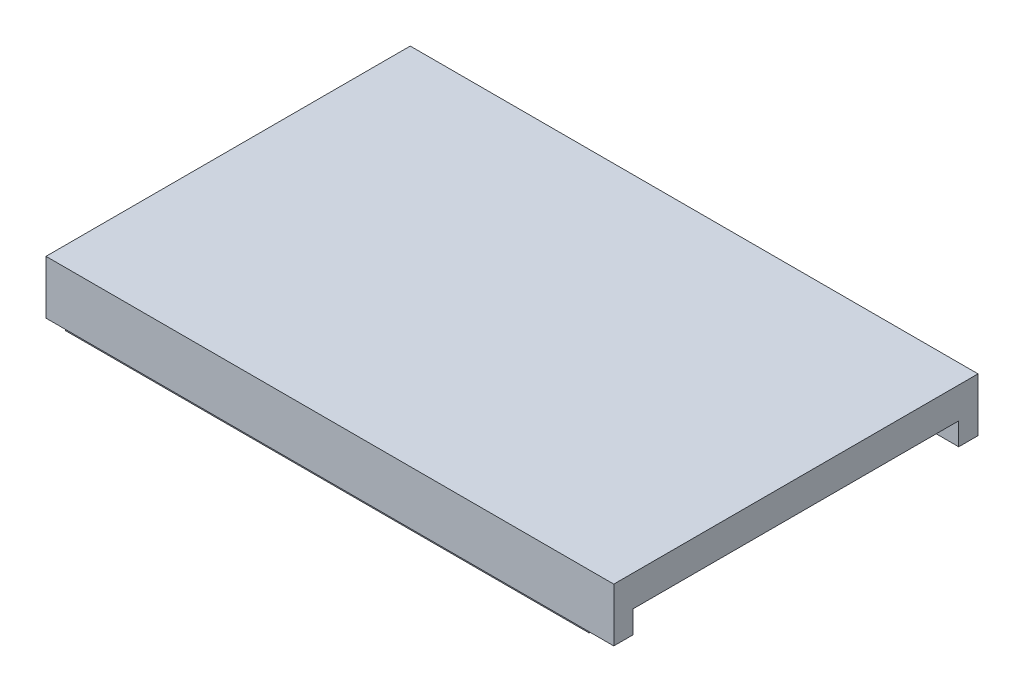
SolidWorks part; units mm, degrees
ref_plane "Front Plane" through (0, 0, 0) normal (0, 0, 1) x (1, 0, 0)
ref_plane "Top Plane" through (0, 0, 0) normal (0, 1, 0) x (1, 0, 0)
ref_plane "Right Plane" through (0, 0, 0) normal (1, 0, 0) x (0, 0, -1)
sketch "Sketch1" plane through (0, 0, 0) normal (0, 1, 0) x (1, 0, 0)
  line L1 (0, 0) -> (53, 0)
  line L2 (0, 0) -> (0, 34)
  line L3 (0, 34) -> (53, 34)
  line L4 (53, 0) -> (53, 34)
  dimension "D1" = 53
  dimension "D2" = 34
extrude "Boss-Extrude1" add sketch "Sketch1" along normal blind 5
sketch "Sketch2" plane through (0, 0, 0) normal (0, -1, 0) x (1, 0, 0)
  line L0 (0, -34) -> (0, 0) construction
  line L1 (1.2, -1.2) -> (49.8, -1.2)
  line L2 (1.2, -1.2) -> (1.2, -32.8)
  line L3 (1.2, -32.8) -> (49.8, -32.8)
  line L4 (49.8, -1.2) -> (49.8, -32.8)
  line L5 (0, 0) -> (53, 0) construction
  line L6 (53, -34) -> (0, -34) construction
  line L7 (53, 0) -> (53, -34) construction
  dimension "D1" = 1.2
  dimension "D2" = 1.2
  dimension "D3" = 1.2
  dimension "D4" = 3.2
extrude "Cut-Extrude1" cut sketch "Sketch2" against normal blind 3.5
sketch "Sketch3" plane through (0, 0, 0) normal (0, -1, 0) x (1, 0, 0)
  line L0 (49.8, -1.2) -> (1.2, -1.2)
  line L1 (1.2, -1.2) -> (1.2, -12)
  line L2 (1.2, -1.2) -> (1.2, -32.8) construction
  line L3 (1.2, -22) -> (1.2, -32.8)
  line L4 (1.2, -32.8) -> (49.8, -32.8)
  line L5 (49.8, -0.9) -> (0.9, -0.9)
  line L6 (0.9, -0.9) -> (0.9, -12)
  line L7 (0.9, -22) -> (0.9, -33.1)
  line L8 (0.9, -33.1) -> (49.8, -33.1)
  line L9 (49.8, -0.9) -> (49.8, -1.2)
  line L10 (0.9, -12) -> (1.2, -12)
  line L11 (0.9, -22) -> (1.2, -22)
  line L12 (49.8, -32.8) -> (49.8, -33.1)
  dimension "D1" = 10.8
  dimension "D2" = 10.8
  dimension "D3" = 0.3
  dimension "D4" = 0.3
extrude "Boss-Extrude2" add sketch "Sketch3" along normal blind 1
sketch "Sketch4" plane through (0, 0, 0) normal (0, -1, 0) x (1, 0, 0)
  line L0 (0, -34) -> (0, 0) construction
  line L1 (1.2, -12) -> (0, -12)
  line L2 (1.2, -12) -> (1.2, -22)
  line L3 (1.2, -22) -> (0, -22)
  line L4 (0, -12) -> (0, -22)
  dimension "D1" = 10
extrude "Cut-Extrude2" cut sketch "Sketch4" against normal blind 0.5
sketch "Sketch5" plane through (0, 0, 0) normal (0, -1, 0) x (1, 0, 0)
  line L0 (49.8, -32.8) -> (49.8, -1.2) construction
  line L1 (49.8, -1.8) -> (53, -1.8)
  line L2 (49.8, -1.8) -> (49.8, -32.2)
  line L3 (49.8, -32.2) -> (53, -32.2)
  line L4 (53, -1.8) -> (53, -32.2)
  line L5 (53, 0) -> (53, -34) construction
  line L6 (0, 0) -> (53, 0) construction
  dimension "D1" = 1.8
  dimension "D2" = 30.4
extrude "Cut-Extrude3" cut sketch "Sketch5" against normal blind 2.1
sketch "Sketch6" plane through (0, 3.5, 0) normal (0, -1, 0) x (1, 0, 0)
  line L1 (1.2, -1.2) -> (6.6, -1.2)
  line L2 (1.2, -1.2) -> (1.2, -6.6)
  line L3 (1.2, -6.6) -> (6.6, -6.6)
  line L4 (6.6, -1.2) -> (6.6, -6.6)
  line L5 (1.2, -32.8) -> (6.6, -32.8)
  line L6 (1.2, -32.8) -> (1.2, -28.5)
  line L7 (1.2, -28.5) -> (6.6, -28.5)
  line L8 (6.6, -32.8) -> (6.6, -28.5)
  dimension "D1" = 5.4
  dimension "D2" = 5.4
  dimension "D3" = 5.4
  dimension "D4" = 4.3
extrude "Boss-Extrude3" add sketch "Sketch6" along normal blind 3
sketch "Sketch7" plane through (0, 0.5, 0) normal (0, -1, 0) x (1, 0, 0)
  line L0 (5, -5) -> (5, -30.5) construction
  line L1 (0, -12) -> (0, 0) construction
  line L2 (0, 0) -> (53, 0) construction
  circle A0 centre (5, -5) radius 1.6
  circle A1 centre (5, -30.5) radius 1.6
  dimension "D4" = 3.2
  dimension "D5" = 3.2
  dimension "D1" = 5
  dimension "D2" = 5
  dimension "D3" = 25.5
extrude "Boss-Extrude4" add sketch "Sketch7" along normal blind 1.2
sketch "Sketch8" plane through (0, -0.7, 0) normal (0, -1, 0) x (1, 0, 0)
  line L0 (5, -5) -> (5, -30.5) construction
  circle A0 centre (5, -5) radius 1
  circle A1 centre (5, -30.5) radius 1
  dimension "D1" = 2
  dimension "D2" = 2
extrude "Cut-Extrude4" cut sketch "Sketch8" against normal blind 5.2
ref_plane "Plane1" through (0, -1.7, 0) normal (0, -1, 0) x (-1, 0, 0)
sketch "Sketch11" plane through (0, -1.7, 0) normal (0, -1, 0) x (-1, 0, 0)
  circle A0 centre (-5, 30.5) radius 0.87
  dimension "D1" = 1.74
curve "Helix/Spiral1" pitch 0.4 height 6 radius 0.87 centre (5, -1.7, -30.5) axis (0, 1, 0) start towards (0, 0, -1)
ref_plane "Plane2" through (5, 0, 0) normal (-1, 0, 0) x (0, 0, 1)
sketch "Sketch13" plane through (5, 0, 0) normal (-1, 0, 0) x (0, 0, 1)
  line L0 (-34, 5) -> (-30.5, 5) construction
  line L1 (-34, 5) -> (0, 5) construction
  line L3 (-30.5, 5) -> (-30.5, -1.7) construction
  line L5 (-30.5, -1.7) -> (-31.2835, -1.7) construction
  line L6 (-30.5, -1.7) -> (-30.5, -3.2) construction
  line L7 (-30.5, -3.2) -> (-31.5, -3.2) construction
  line L8 (-31.5, -3.2) -> (-31.5, -1.2) construction
  line L9 (-31.2835, -1.7) -> (-32.0835, -1.7) construction
  line L10 (-31.2835, -1.75) -> (-31.2835, -1.65) construction
  line L11 (-31.2835, -1.65) -> (-31.7165, -1.4) construction
  line L16 (-31.2835, -1.75) -> (-31.7165, -2) construction
  line L17 (-31.2835, -1.65) -> (-31.5, -1.525)
  line L21 (-31.5, -1.525) -> (-31.5, -1.875)
  line L22 (-31.5, -1.875) -> (-31.2835, -1.75)
  line L23 (-31.2835, -1.75) -> (-31.2835, -1.65)
  dimension "D1" = 3.5
  dimension "D3" = 6.7
  dimension "D5" = 0.7835
  dimension "D6" = 1.5
  dimension "D7" = 1
  dimension "D8" = 2
  dimension "D9" = 0.8
  dimension "D10" = 90
  dimension "D11" = 0.05
  dimension "D12" = 0.1
  dimension "D13" = 0.5
  dimension "D14" = 0.5
  dimension "D15" = 30
  dimension "D16" = 60
  dimension "D17" = 0.35
sweep "Sweep2" add profiles "Sketch13" path "Helix/Spiral1"
pattern_linear "LPattern1" count 2 spacing 25.5 along (0, 0, 1) of "Sweep2"
sketch "Sketch14" plane through (5, 0, 0) normal (-1, 0, 0) x (0, 0, 1)
  line L5 (-34, 5) -> (-34, 0) construction
  line L10 (-32.5, -0.7) -> (-28.5, -0.7)
  line L11 (-32.5, -0.7) -> (-32.5, -3.7)
  line L12 (-32.5, -3.7) -> (-28.5, -3.7)
  line L13 (-28.5, -0.7) -> (-28.5, -3.7)
  line L14 (-32.5, -0.7) -> (-28.5, -3.7) construction
  line L15 (-32.5, -3.7) -> (-28.5, -0.7) construction
  line L16 (-34, 5) -> (0, 5) construction
  line L18 (-7, -0.7) -> (-3, -0.7)
  line L19 (-7, -0.7) -> (-7, -3.7)
  line L20 (-7, -3.7) -> (-3, -3.7)
  line L21 (-3, -0.7) -> (-3, -3.7)
  line L22 (-7, -0.7) -> (-3, -3.7) construction
  line L23 (-7, -3.7) -> (-3, -0.7) construction
  point P0 (-30.5, -2.2)
  point P9 (-5, -2.2)
  dimension "D1" = 3.5
  dimension "D2" = 5.7
  dimension "D3" = 3
  dimension "D4" = 4
  dimension "D5" = 5.7
  dimension "D6" = 25.5
  dimension "D7" = 3
  dimension "D8" = 4
extrude "Cut-Extrude5" cut sketch "Sketch14" against normal blind 1.5 and the other way blind 1.5
sketch "Sketch15" plane through (5, 0, 0) normal (-1, 0, 0) x (0, 0, 1)
  line L0 (-34, 5) -> (-30.5, 5) construction
  line L1 (-34, 5) -> (0, 5) construction
  line L2 (-30.5, 5) -> (-30.5, -0.7) construction
  line L3 (-30.5, -0.7) -> (-31.5, -0.7) construction
  line L4 (-31.5, -0.7) -> (-31.1, -0.4691)
  line L5 (-31.1, -0.4691) -> (-31.1, -0.7)
  line L6 (-31.1, -0.7) -> (-31.5, -0.7)
  dimension "D1" = 3.5
  dimension "D2" = 5.7
  dimension "D3" = 1
  dimension "D4" = 0.4
  dimension "D5" = 30
revolve "Cut-Revolve1" cut sketch "Sketch15" angle 360 about L2
pattern_linear "LPattern2" count 2 spacing 25.5 along (0, 0, 1) of "Cut-Revolve1"
